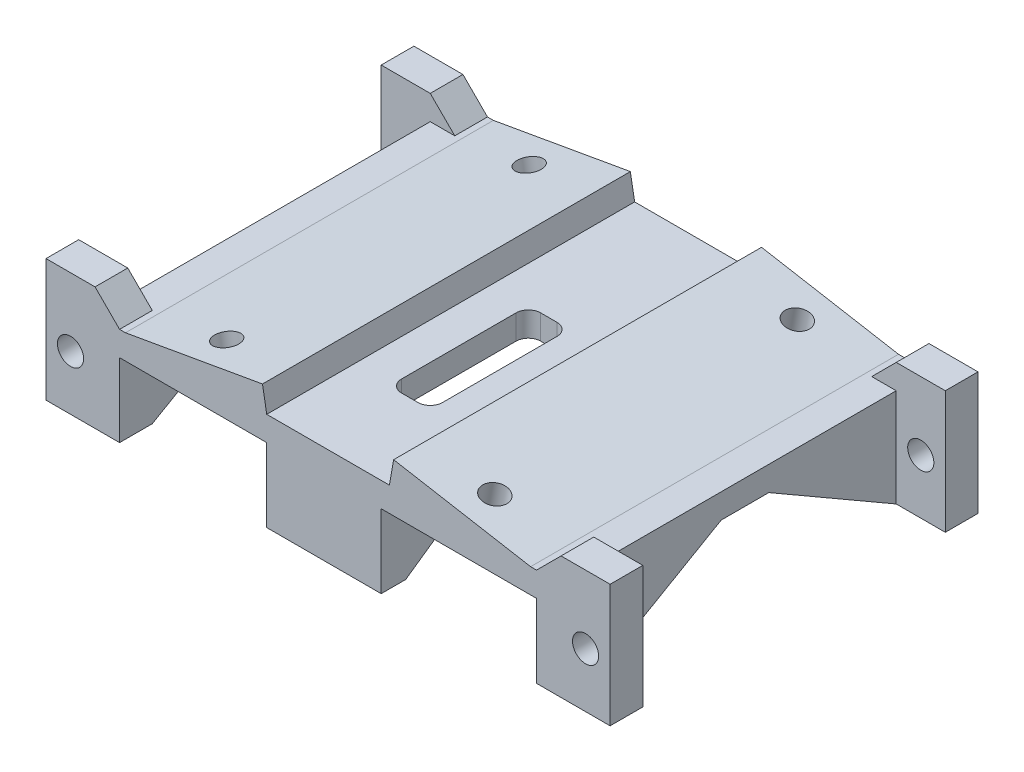
SolidWorks part; units mm, degrees
ref_plane "前视基准面" through (0, 0, 0) normal (0, 0, 1) x (1, 0, 0)
ref_plane "上视基准面" through (0, 0, 0) normal (0, 1, 0) x (1, 0, 0)
ref_plane "右视基准面" through (0, 0, 0) normal (1, 0, 0) x (0, 0, -1)
sketch "草图1" plane through (0, 0, 0) normal (0, 1, 0) x (1, 0, 0)
  line L1 (0, 0) -> (57, 0)
  line L2 (0, 0) -> (0, 45)
  line L3 (0, 45) -> (57, 45)
  line L4 (57, 0) -> (57, 45)
  dimension "D1" = 45
  dimension "D2" = 57
extrude "凸台-拉伸1" add sketch "草图1" along normal blind 3
sketch "草图2" plane through (0, 0, 0) normal (-1, 0, 0) x (0, 0, 1)
  line L0 (0, 6) -> (-4, 6)
  line L1 (-4, 6) -> (-4, -9)
  line L2 (-4, -9) -> (0, -9)
  line L3 (0, -9) -> (0, 6)
  line L4 (-45, 3) -> (0, 3) construction
  line L5 (-45, 0) -> (0, 0) construction
  line L8 (0, 3) -> (0, 0) construction
  dimension "D1" = 3
  dimension "D2" = 9
  dimension "D3" = 4
extrude "凸台-拉伸2" add sketch "草图2" along normal blind 6
sketch "草图3" plane through (57, 0, 0) normal (1, 0, 0) x (0, 0, -1)
  line L0 (0, 6) -> (0, -9)
  line L1 (0, -9) -> (4, -9)
  line L2 (4, -9) -> (4, 6)
  line L3 (4, 6) -> (0, 6)
extrude "凸台-拉伸3" add sketch "草图3" along normal blind 6
sketch "草图4" plane through (57, 0, 0) normal (-1, 0, 0) x (0, 0, 1)
  line L0 (-4, -9) -> (-19.5885, 0)
  line L1 (-4, 0) -> (-45, 0) construction
  line L2 (-19.5885, 0) -> (0, 0)
  line L3 (0, 0) -> (0, -9)
  line L4 (0, -9) -> (-4, -9)
  dimension "D1" = 30
extrude "凸台-拉伸4" add sketch "草图4" along normal blind 3
sketch "草图5" plane through (0, 0, 0) normal (1, 0, 0) x (0, 0, -1)
  line L0 (0, 0.3045) -> (0, -9)
  line L1 (0, -9) -> (4, -9)
  line L2 (4, -9) -> (19.5885, 0)
  line L3 (45, 0) -> (4, 0) construction
  line L4 (19.5885, 0) -> (0, 0)
  line M3 (4, -9) -> (4, 0)
  line M4 (4, 0) -> (0, 0)
  line M5 (0, 0) -> (0, -9)
  line M6 (0, -9) -> (4, -9)
  dimension "D1" = 30
extrude "凸台-拉伸5" add sketch "草图5" along normal blind 3 contours L2 L4 M3 | M6 M3 M4 M5 region at (0, -4.5, -2) region at (0, -3, -9.1962)
chamfer "倒角1" distance 3 angle 45 2 edges at (0, 3, -2) (57, 3, -2)
sketch "草图6" plane through (0, 0, -4) normal (0, 0, -1) x (-1, 0, 0)
  line L0 (-60, -2.3233) -> (3, -2.3233) construction
  line L1 (-63, -9) -> (-63, 6) construction
  line L2 (6, 6) -> (6, -9) construction
  circle A0 centre (3, -2.3233) radius 1.6
  circle A1 centre (-60, -2.3233) radius 1.6
  dimension "D1" = 3
  dimension "D2" = 3
extrude "切除-拉伸1" cut sketch "草图6" against normal blind 4
sketch "草图7" plane through (0, 3, 0) normal (0, 1, 0) x (1, 0, 0)
  line L0 (28, 49.7957) -> (28, -5.721) construction
  line L1 (8, 41) -> (8, 4)
  line L2 (3, 0) -> (54, 0) construction
  line L3 (0, 45) -> (0, 4) construction
  line L4 (48, 41) -> (48, 4)
  circle A0 centre (8, 41) radius 1.6
  circle A1 centre (8, 4) radius 1.6
  circle A2 centre (48, 4) radius 1.6
  circle A3 centre (48, 41) radius 1.6
  dimension "D1" = 37
  dimension "D2" = 4
  dimension "D3" = 8
extrude "切除-拉伸2" [suppressed] cut sketch "草图7" against normal blind 3 contours A3 | A2 | A0 | A1
sketch "草图8" plane through (0, 0, 0) normal (0, -1, 0) x (1, 0, 0)
  line L0 (24, -45) -> (32, -45)
  line L1 (57, -45) -> (0, -45) construction
  line L2 (32, -45) -> (32, -42)
  line L3 (32, -42) -> (24, -42)
  line L4 (24, -42) -> (24, -45)
  line L5 (28, 5.34) -> (28, -50.6665) construction
  line L6 (0, -45) -> (0, -19.5885) construction
  point P10 (32, -43.5)
  dimension "D1" = 28
  dimension "D2" = 3
  dimension "D3" = 8
  dimension "D4" = 4
extrude "凸台-拉伸6" add sketch "草图8" along normal blind 9
sketch "草图9" plane through (32, 0, 0) normal (1, 0, 0) x (0, 0, -1)
  line L0 (45, 0) -> (29.1467, 0)
  line L1 (29.1467, 0) -> (42, -9)
  line L2 (42, -9) -> (45, -9)
  line L3 (45, -9) -> (45, 0)
  dimension "D1" = 35
extrude "凸台-拉伸7" add sketch "草图9" along normal blind 3
sketch "草图10" plane through (24, 0, 0) normal (-1, 0, 0) x (0, 0, 1)
  line L0 (-45, 0) -> (-45, -9)
  line L1 (-45, -9) -> (-42, -9)
  line L2 (-42, -9) -> (-29.1467, 0)
  line L3 (-29.1467, 0) -> (-45, 0)
extrude "凸台-拉伸8" add sketch "草图10" along normal blind 3
sketch "草图11" plane through (0, 0, -42) normal (0, 0, 1) x (1, 0, 0)
  line L0 (24, -9) -> (24, 0) construction
  line L1 (32, -9) -> (24, -9) construction
  circle A0 centre (28, -4.5) radius 1.6
  dimension "D1" = 4
  dimension "D2" = 4.5
extrude "切除-拉伸3" [suppressed] cut sketch "草图11" against normal blind 3
sketch "草图12" plane through (0, 3, 0) normal (0, 1, 0) x (1, 0, 0)
  line L0 (28, 49.4691) -> (28, -3.816) construction
  line L1 (25.5, 27.5) -> (25.5, 10.5)
  line L2 (25.5, 10.5) -> (30.5, 10.5)
  line L3 (30.5, 10.5) -> (30.5, 27.5)
  line L4 (30.5, 27.5) -> (25.5, 27.5)
  line L5 (0, 45) -> (0, 4) construction
  line L6 (-5.009, 22.5) -> (59.3487, 22.5) construction
  line L7 (3, 0) -> (54, 0) construction
  dimension "D1" = 28
  dimension "D2" = 2.5
  dimension "D3" = 2.5
  dimension "D4" = 22.5
  dimension "D5" = 5
  dimension "D6" = 12
extrude "切除-拉伸4" cut sketch "草图12" against normal blind 3
fillet "圆角1" radius 1.5 4 edges at (30.5, 1.5, -10.5) (25.5, 1.5, -10.5) (25.5, 1.5, -27.5) (30.5, 1.5, -27.5)
ref_plane "基准面1" through (28.5, 0, 0) normal (1, 0, 0) x (0, 0, -1)
sketch "草图13" plane through (0, 3, 0) normal (0, 1, 0) x (1, 0, 0)
  line L0 (36, 45) -> (36, 0) construction
  line L1 (57, 45) -> (0, 45) construction
  line L2 (3, 0) -> (54, 0) construction
  line L3 (57, 4) -> (57, 45) construction
  dimension "D1" = 21
ref_plane "基准面2" through (34.4014, -6.0659, 0) normal (0.9848, -0.1736, 0) x (0, 0, 1)
sketch "草图14" plane through (34.4014, -6.0659, 0) normal (0.9848, -0.1736, 0) x (0, 0, 1)
  line L0 (-45, -9.2058) -> (0, -9.2058) construction
  line L1 (-45, -9.2058) -> (0, -9.2058) construction
  line L3 (-45, -9.2058) -> (0, -9.2058) construction
  line L4 (-45, -9.2058) -> (-45, -12.2058) construction
  line L5 (-45, -12.2058) -> (0, -12.2058) construction
  line L6 (0, -9.2058) -> (0, -12.2058) construction
  dimension "D1" = 3
ref_plane "基准面3" through (2.1195, 12.0203, 0) normal (0.1736, 0.9848, 0) x (0, 0, 1)
sketch "草图15" plane through (2.1195, 12.0203, 0) normal (0.1736, 0.9848, 0) x (0, 0, 1)
  line L1 (-45, 34.9321) -> (0, 34.9321)
  line L2 (-45, 34.9321) -> (-45, 52.6587)
  line L3 (-45, 52.6587) -> (0, 52.6587)
  line L4 (0, 34.9321) -> (0, 52.6587)
extrude "凸台-拉伸9" add sketch "草图15" against normal up to body separate body
sketch "草图16" plane through (2.1195, 12.0203, 0) normal (0.1736, 0.9848, 0) x (0.9848, -0.1736, 0)
  line L0 (43.4391, 45) -> (43.4391, 0) construction
  line L1 (51.946, 45) -> (34.9321, 45) construction
  line L2 (34.9321, 0) -> (51.946, 0) construction
  line L3 (51.946, 22.5) -> (43.4391, 22.5) construction
  line L4 (51.946, 45) -> (51.946, 0) construction
  circle A0 centre (43.4391, 41) radius 1.5
  circle A1 centre (43.4391, 4) radius 1.5
  dimension "D1" = 3
  dimension "D2" = 18.5
extrude "切除-拉伸5" cut sketch "草图16" against normal through all
mirror "镜向1" about plane through (28.5, 0, 0) normal (1, 0, 0) of "切除-拉伸5", "凸台-拉伸9"
ref_plane "基准面4" through (0, 0, -22.5) normal (0, 0, 1) x (1, 0, 0)
mirror "镜向2" about plane through (0, 0, -22.5) normal (0, 0, 1) of "倒角1", "凸台-拉伸5", "凸台-拉伸4", "凸台-拉伸3", "凸台-拉伸2", "切除-拉伸1"
mirror "镜向3" about plane through (0, 0, -22.5) normal (0, 0, 1) of "凸台-拉伸7", "凸台-拉伸6", "凸台-拉伸8"
